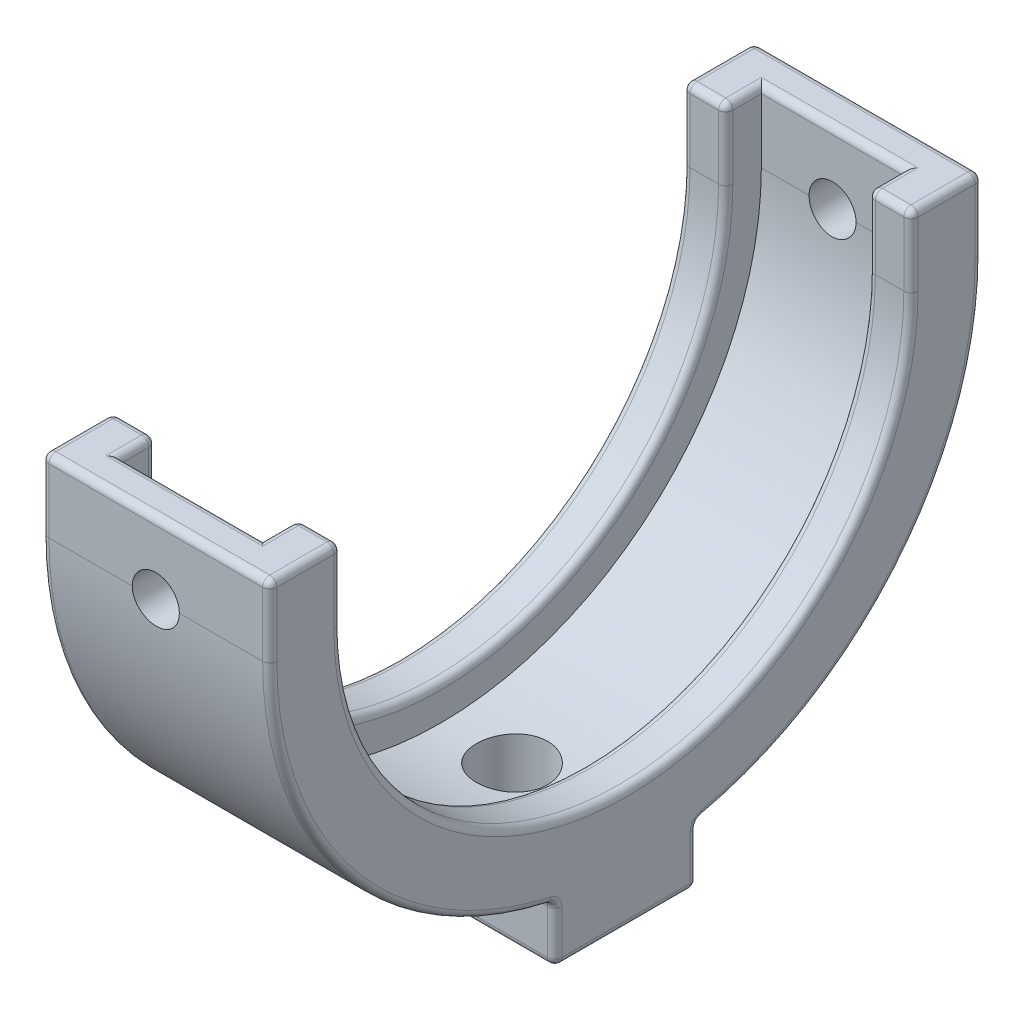
SolidWorks part; units mm, degrees
ref_plane "Front Plane" through (0, 0, 0) normal (0, 0, 1) x (1, 0, 0)
ref_plane "Top Plane" through (0, 0, 0) normal (0, 1, 0) x (1, 0, 0)
ref_plane "Right Plane" through (0, 0, 0) normal (1, 0, 0) x (0, 0, -1)
sketch "Sketch1" plane through (0, 0, 0) normal (1, 0, 0) x (0, 0, -1)
  line L0 (-25, 0) -> (25, 0)
  line L3 (-5, -24.4949) -> (-5, -28.4949)
  line L4 (-5, -28.4949) -> (5, -28.4949)
  line L5 (5, -24.4949) -> (5, -28.4949)
  arc A0 (-25, 0) -> (-5, -24.4949) centre (0, 0) ccw
  arc A1 (5, -24.4949) -> (25, 0) centre (0, 0) ccw
  dimension "D1" = 25
  dimension "D2" = 10
  dimension "D3" = 4
extrude "Boss-Extrude1" add sketch "Sketch1" along normal blind 16
sketch "Sketch2" plane through (0, 0, 0) normal (0, 1, 0) x (1, 0, 0)
  line L0 (16, -25) -> (0, -25) construction
  line L1 (3, -22.5) -> (13, -22.5)
  line L2 (3, -22.5) -> (3, -20)
  line L3 (3, 0) -> (13, 0)
  line L4 (13, -22.5) -> (13, -20)
  line L5 (16, 25) -> (16, -25) construction
  line L6 (13, -20) -> (16, -20)
  line L7 (16, 25) -> (16, -25) construction
  line L8 (13, 0) -> (16, 0)
  line L9 (16, -20) -> (16, 0)
  line L10 (8, -25) -> (8, 25) construction
  line L11 (16, 25) -> (0, 25) construction
  line L12 (3, 0) -> (0, 0)
  line L13 (0, -20) -> (0, 0)
  line L14 (3, -20) -> (0, -20)
  point P4 (8, -22.5)
  point P7 (8, -25)
  point P10 (8, 0)
  point P11 (16, 0)
  dimension "D1" = 10
  dimension "D2" = 22.5
  dimension "D3" = 5
revolve "Cut-Revolve3" cut sketch "Sketch2" angle 360 about L3
sketch "Sketch18" plane through (0, 0, 0) normal (0, 1, 0) x (1, 0, 0)
  line L8 (16, -25) -> (16, -20)
  line L9 (16, -20) -> (13, -20)
  line L10 (13, -20) -> (13, -22.5)
  line L11 (13, -22.5) -> (3, -22.5)
  line L12 (3, -22.5) -> (3, -20)
  line L13 (3, -20) -> (0, -20)
  line L14 (0, -20) -> (0, -25)
  line L15 (0, -25) -> (16, -25)
  line L16 (16, -25) -> (16, -20)
  line L17 (16, -20) -> (13, -20)
  line L18 (13, -20) -> (13, -22.5)
  line L19 (13, -22.5) -> (3, -22.5)
  line L20 (3, -22.5) -> (3, -20)
  line L21 (3, -20) -> (0, -20)
  line L22 (0, -20) -> (0, -25)
  line L23 (0, -25) -> (16, -25)
  line L24 (13, 22.5) -> (13, 20)
  line L25 (13, 20) -> (16, 20)
  line L26 (16, 20) -> (16, 25)
  line L27 (16, 25) -> (0, 25)
  line L28 (0, 25) -> (0, 20)
  line L29 (0, 20) -> (3, 20)
  line L30 (3, 20) -> (3, 22.5)
  line L31 (3, 22.5) -> (13, 22.5)
  line L32 (13, 22.5) -> (13, 20)
  line L33 (13, 20) -> (16, 20)
  line L34 (16, 20) -> (16, 25)
  line L35 (16, 25) -> (0, 25)
  line L36 (0, 25) -> (0, 20)
  line L37 (0, 20) -> (3, 20)
  line L38 (3, 20) -> (3, 22.5)
  line L39 (3, 22.5) -> (13, 22.5)
  dimension "D1" = 0
  dimension "D2" = 0
extrude "Boss-Extrude3" add sketch "Sketch18" along normal blind 5
sketch "Sketch19" plane through (0, 0, 25) normal (0, 0, 1) x (1, 0, 0)
  line L0 (16, 0) -> (0, 0) construction
  circle A0 centre (8, 0) radius 1.65
  dimension "D1" = 3.3
extrude "Cut-Extrude1" cut sketch "Sketch19" against normal through all
fillet "Fillet3" radius 0.5 22 edges at (0, 5, 22.5) (1.5, 5, 20) (3, 5, 21.25) (8, 5, 22.5) (13, 5, 21.25) (14.5, 5, 20) (16, 5, 22.5) (8, 5, 25) (3, 5, -21.25) (1.5, 5, -20) (0, 5, -22.5) (8, 5, -25) (16, 5, -22.5) (14.5, 5, -20) (13, 5, -21.25) (8, 5, -22.5) (16, -28.4949, 0) (0, -28.4949, 0) (8, -24.4949, 5) (8, -28.4949, 5) (8, -28.4949, -5) (8, -24.4949, -5)
fillet "Fillet5" radius 0.5 20 edges at (15.8536, 4.8536, 20.1464) (15.8536, 4.8536, -20.1464) (0.1464, 4.8536, 20.1464) (0.1464, 4.8536, -20.1464) (13.1464, 4.8536, -20.1464) (13.1464, 4.8536, 20.1464) (2.8536, 4.8536, 20.1464) (2.8536, 4.8536, -20.1464) (16, 2.25, -20) (16, -20, 0) (16, 2.25, 20) (0, 2.25, -20) (0, -20, 0) (0, 2.25, 20) (13, 2.25, 20) (13, -20, 0) (13, 2.25, -20) (3, 2.25, -20) (3, -20, 0) (3, 2.25, 20)
fillet "Fillet6" radius 0.5 24 edges at (0.1464, -28.3485, -4.8536) (0.1464, 4.8536, -24.8536) (0.1464, 4.8536, 24.8536) (0.1464, -28.3485, 4.8536) (15.8536, 4.8536, 24.8536) (15.8536, -28.3485, 4.8536) (15.8536, -28.3485, -4.8536) (15.8536, 4.8536, -24.8536) (0, 2.25, -25) (0, -15.6556, -19.4911) (16, -26.4473, -5) (0, -24.5867, -5.1102) (0, -26.4473, -5) (0, -26.4473, 5) (16, -26.4473, 5) (0, -24.5867, 5.1102) (0, -15.6556, 19.4911) (0, 2.25, 25) (16, 2.25, 25) (16, -15.6556, 19.4911) (16, -24.5867, 5.1102) (16, -24.5867, -5.1102) (16, 2.25, -25) (16, -15.6556, -19.4911)
sketch "Sketch20" plane through (0, -28.4949, 0) normal (0, -1, 0) x (1, 0, 0)
  line L0 (15.5, 4.5) -> (0.5, 4.5) construction
  line L1 (15.5, -4.5) -> (15.5, 4.5) construction
  point P0 (8, 0)
  point P1 (0, 0)
  point P4 (8, 4.5)
  point P7 (15.5, 0)
hole_wizard "M6x1.0 Tapped Hole1" positions "Sketch21" profile "Sketch22" tap size "M6x1.0" standard "BSI" end condition through all
sketch "Sketch21" plane through (0, -28.4949, 0) normal (0, -1, 0) x (-1, 0, 0)
  point P0 (-8, 0)
sketch "Sketch22" plane through (8, -28.4949, 0) normal (1, 0, 0) x (0, 0, -1)
  line L0 (0, 0) -> (0, 33.4949)
  line L1 (0, 33.4949) -> (2.5, 33.4949)
  line L2 (2.5, 33.4949) -> (2.5, 0)
  line L5 (2.5, 0) -> (0, 0)
  line L11 (0, -6.35) -> (0, 107.95) construction
  dimension "Thru Tap Drill Dia." = 5
  dimension "Thru Tap Drill Depth" = 33.4949
cosmetic thread "Hole Thread1" parameters "D2"=6
